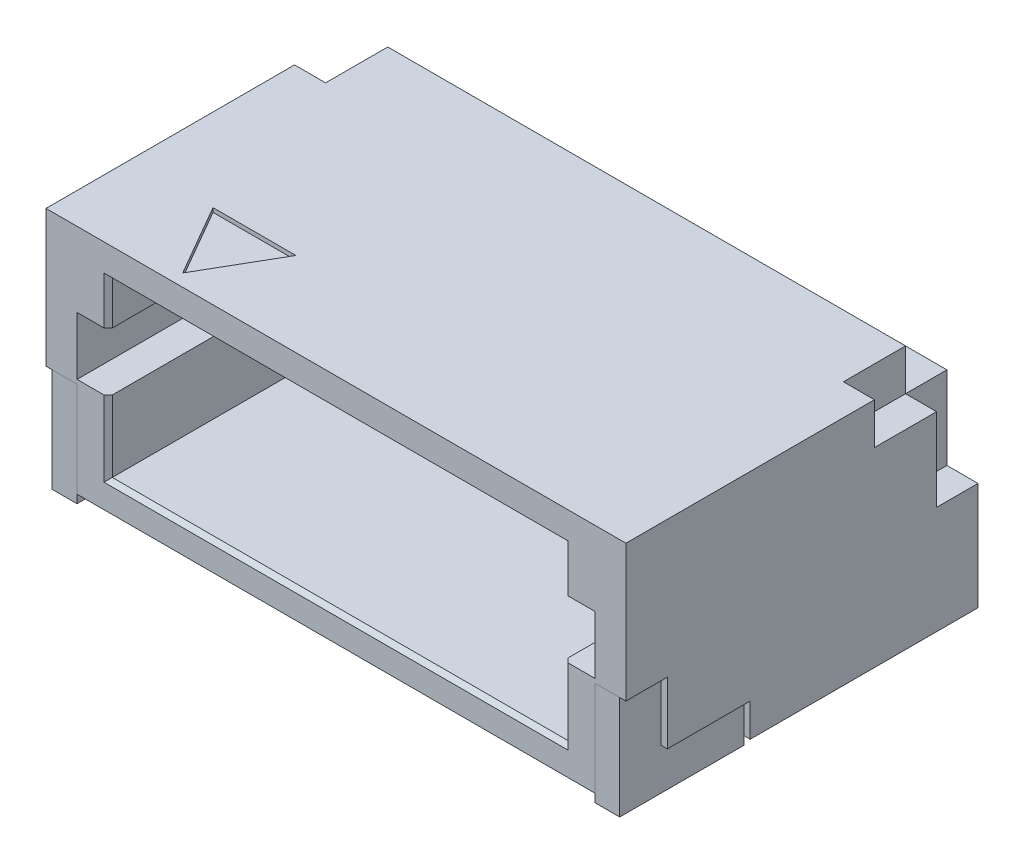
SolidWorks part; units mm, degrees
ref_plane "Front Plane" through (0, 0, 0) normal (0, 0, 1) x (1, 0, 0)
ref_plane "Top Plane" through (0, 0, 0) normal (0, 1, 0) x (1, 0, 0)
ref_plane "Right Plane" through (0, 0, 0) normal (1, 0, 0) x (0, 0, -1)
ref_plane "Right Plane .5mm offset" through (0.5, 0, 0) normal (1, 0, 0) x (0, 0, -1)
sketch "Sketch1" plane through (0, 0, 0) normal (1, 0, 0) x (0, 0, -1)
  line L1 (-4.25, 0) -> (0, 0)
  line L2 (-4.25, 0) -> (-4.25, 2.9)
  line L3 (-4.25, 2.9) -> (0, 2.9)
  line L4 (0, 0) -> (0, 2.9)
  dimension "D1" = 4.25
  dimension "D2" = 2.9
extrude "Extrude1" add sketch "Sketch1" along normal mid plane 7
sketch "Sketch2" plane through (0, 0, 4.25) normal (0, 0, 1) x (1, 0, 0)
  line L0 (2.75, 2) -> (3.125, 2)
  line L1 (-2.75, 0.4375) -> (2.75, 0.4375)
  line L2 (-2.75, 0.4375) -> (-2.75, 1.3)
  line L3 (-2.75, 2.525) -> (2.75, 2.525)
  line L4 (2.75, 0.4375) -> (2.75, 1.3)
  line L5 (3.125, 2) -> (3.125, 1.3)
  line L6 (3.125, 1.3) -> (2.75, 1.3)
  line L7 (-2.75, 2) -> (-3.125, 2)
  line L8 (-3.125, 2) -> (-3.125, 1.3)
  line L9 (-3.125, 1.3) -> (-2.75, 1.3)
  line L10 (2.75, 2) -> (2.75, 2.525)
  line L11 (-2.75, 2) -> (-2.75, 2.525)
  line L12 (-3.5, 2.9) -> (-3.5, 0) construction
  line L13 (3.5, 2.9) -> (3.5, 0) construction
  line L14 (3.5, 2.9) -> (-3.5, 2.9) construction
  line L15 (3.5, 0) -> (-3.5, 0) construction
  dimension "D1" = 2.75
  dimension "D2" = 2.75
  dimension "D3" = 0.375
  dimension "D4" = 0.375
  dimension "D5" = 0.375
  dimension "D6" = 0.4375
  dimension "D7" = 1.6
  dimension "D8" = 0.9
extrude "Extrude2" cut sketch "Sketch2" against normal blind 3.25
sketch "Sketch3" plane through (0, 0, 1) normal (0, 0, 1) x (1, 0, 0)
  line L1 (-0.1, 2.2) -> (0.1, 2.2)
  line L2 (-0.1, 2.2) -> (-0.1, 1.6)
  line L3 (-0.1, 1.6) -> (0.1, 1.6)
  line L4 (0.1, 2.2) -> (0.1, 1.6)
  line L5 (3.5, 2.9) -> (-3.5, 2.9) construction
  point P4 (0, 1.6)
  dimension "D1" = 0.2
  dimension "D2" = 1.3
  dimension "D3" = 0.7
extrude "Extrude3" add sketch "Sketch3" along normal blind 2.25
pattern_linear "LPattern1" count 3 spacing 1 along (-1, 0, 0) count 3 spacing 1 along (1, 0, 0) of "Extrude3"
chamfer "Chamfer1" distance 2 distance2 0.2 10 edges at (0, 1.6, 3.25) (0, 2.2, 3.25) (-2, 2.2, 3.25) (-1, 2.2, 3.25) (2, 2.2, 3.25) (2, 1.6, 3.25) (1, 1.6, 3.25) (-2, 1.6, 3.25) (-1, 1.6, 3.25) (1, 2.2, 3.25) first distance on face at (0, 1.6, 2.125) first distance on face at (0, 2.2, 2.125) first distance on face at (-2, 2.2, 2.125) first distance on face at (-1, 2.2, 2.125) first distance on face at (2, 2.2, 2.125) first distance on face at (2, 1.6, 2.125) first distance on face at (1, 1.6, 2.125) first distance on face at (-2, 1.6, 2.125) first distance on face at (-1, 1.6, 2.125) first distance on face at (1, 2.2, 2.125)
fillet "Fillet1" radius 0.025 40 edges at (2, 1.8, 3.25) (1.9, 1.9, 3.25) (2, 2, 3.25) (2.1, 1.9, 3.25) (1, 1.8, 3.25) (0.9, 1.9, 3.25) (1, 2, 3.25) (1.1, 1.9, 3.25) (0, 2, 3.25) (0.1, 1.9, 3.25) (0, 1.8, 3.25) (-0.1, 1.9, 3.25) (-1, 1.8, 3.25) (-1.1, 1.9, 3.25) (-1, 2, 3.25) (-0.9, 1.9, 3.25) (-2, 1.8, 3.25) (-2.1, 1.9, 3.25) (-2, 2, 3.25) (-1.9, 1.9, 3.25) (-2.1, 2.1, 2.25) (-1.9, 2.1, 2.25) (-2.1, 1.7, 2.25) (-1.9, 1.7, 2.25) (-0.1, 1.7, 2.25) (0.1, 2.1, 2.25) (-0.1, 2.1, 2.25) (0.1, 1.7, 2.25) (2.1, 2.1, 2.25) (1.9, 2.1, 2.25) (2.1, 1.7, 2.25) (1.9, 1.7, 2.25) (0.9, 1.7, 2.25) (1.1, 1.7, 2.25) (1.1, 2.1, 2.25) (0.9, 2.1, 2.25) (-0.9, 2.1, 2.25) (-1.1, 2.1, 2.25) (-1.1, 1.7, 2.25) (-0.9, 1.7, 2.25)
sketch "Sketch4" plane through (3.5, 0, 0) normal (1, 0, 0) x (0, 0, -1)
  line L0 (-4.25, 1.25) -> (-3.75, 1.25)
  line L1 (-4.25, 2.9) -> (-4.25, 0) construction
  line L2 (-3.75, 1.25) -> (-3.75, 0.5)
  line L3 (-3.75, 0.5) -> (-2.75, 0.5)
  line L4 (-2.75, 0.5) -> (-2.75, 0)
  line L5 (-4.25, 0) -> (0, 0) construction
  line L6 (-4.25, 1.25) -> (-4.25, 0)
  line L7 (-4.25, 0) -> (-2.75, 0)
  line L8 (-1.25, 2.9) -> (-1.25, 2.4)
  line L9 (0, 2.9) -> (-4.25, 2.9) construction
  line L10 (-1.25, 2.4) -> (-0.5, 2.4)
  line L11 (-0.5, 2.4) -> (-0.5, 1.4)
  line L12 (-0.5, 1.4) -> (0, 1.4)
  line L13 (0, 0) -> (0, 2.9) construction
  line L14 (0, 1.4) -> (0, 2.9)
  line L15 (-1.25, 2.9) -> (0, 2.9)
  dimension "D1" = 0.5
  dimension "D2" = 0.5
  dimension "D3" = 1.5
  dimension "D4" = 1.25
  dimension "D5" = 0.5
  dimension "D6" = 1.5
  dimension "D7" = 1.25
  dimension "D8" = 0.5
extrude "Extrude4" cut sketch "Sketch4" against normal blind 0.375
mirror "Mirror1" about plane through (0, 0, 0) normal (1, 0, 0) of "Extrude4"
sketch "Sketch8" plane through (3.125, 0, 0) normal (1, 0, 0) x (0, 0, -1)
  line L4 (-2.75, 0.5) -> (-3.75, 0.5)
  line L5 (-2.75, 0.5) -> (-3.75, 0.5)
  line L6 (-4.25, 1.25) -> (-4.25, 0)
  line L7 (-4.25, 0) -> (-2.75, 0)
  line L8 (-2.75, 0) -> (-2.75, 0.5)
  line L11 (-3.75, 0.5) -> (-3.75, 1.25)
  line L12 (-4.25, 1.25) -> (-4.25, 0)
  line L13 (-4.25, 0) -> (-2.75, 0)
  line L14 (-2.75, 0) -> (-2.75, 0.5)
  line L15 (-3.75, 0.5) -> (-3.75, 1.25)
  line L16 (-3.75, 1.25) -> (-4.25, 1.25)
  line L17 (-3.75, 1.25) -> (-4.25, 1.25)
  dimension "D1" = 0
extrude "Extrude7" add sketch "Sketch8" along normal blind 0.3 separate body
sketch "Sketch9" plane through (-3.125, 0, 0) normal (-1, 0, 0) x (0, 0, 1)
  line L4 (4.25, 1.25) -> (3.75, 1.25)
  line L5 (4.25, 1.25) -> (3.75, 1.25)
  line L6 (4.25, 0) -> (4.25, 1.25)
  line L9 (3.75, 1.25) -> (3.75, 0.5)
  line L10 (2.75, 0.5) -> (2.75, 0)
  line L11 (2.75, 0) -> (4.25, 0)
  line L12 (4.25, 0) -> (4.25, 1.25)
  line L13 (3.75, 1.25) -> (3.75, 0.5)
  line L14 (3.75, 0.5) -> (2.75, 0.5)
  line L15 (3.75, 0.5) -> (2.75, 0.5)
  line L16 (2.75, 0.5) -> (2.75, 0)
  line L17 (2.75, 0) -> (4.25, 0)
  dimension "D1" = 0
extrude "Extrude8" add sketch "Sketch9" along normal blind 0.3 separate body
sketch "Sketch6" plane through (0, 0, 0) normal (1, 0, 0) x (0, 0, -1)
  line L0 (-0.5, 2.9) -> (-0.5, 2.4)
  line L1 (0, 2.9) -> (-1.25, 2.9) construction
  line L2 (-0.5, 2.4) -> (0, 2.4)
  line L3 (0, 1.4) -> (0, 2.9) construction
  line L4 (0, 2.4) -> (0, 2.9)
  line L5 (0, 2.9) -> (-0.5, 2.9)
extrude "Extrude5" cut sketch "Sketch6" against normal blind 40.375 and the other way blind 40.375
sketch "Sketch7" plane through (0, 0, 0) normal (0, 1, 0) x (1, 0, 0)
  line L0 (-0.1, 0) -> (-0.1, -0.35)
  line L1 (3.125, 0) -> (-3.125, 0) construction
  line L2 (-0.1, -0.35) -> (0.1, -0.35)
  line L3 (0.1, -0.35) -> (0.1, 0)
  line L4 (0.1, 0) -> (-0.1, 0)
  point P4 (0, -0.35)
  dimension "D1" = 0.2
  dimension "D2" = 0.35
extrude "Extrude6" cut sketch "Sketch7" along normal blind 40.375
pattern_linear "LPattern2" count 3 spacing 1 along (1, 0, 0) count 3 spacing 1 along (-1, 0, 0) of "Extrude6"
chamfer "Chamfer2" distance 0.15 angle 45 10 edges at (0.1, 1.2, 0) (-0.1, 1.2, 0) (2.1, 1.2, 0) (1.9, 1.2, 0) (1.1, 1.2, 0) (0.9, 1.2, 0) (-2.1, 1.2, 0) (-1.9, 1.2, 0) (-0.9, 1.2, 0) (-1.1, 1.2, 0)
sketch "Sketch11" plane through (0, 0, 0) normal (0, -1, 0) x (1, 0, 0)
  line L46 (-3.5, 0) -> (-2.25, 0)
  line L47 (-2.25, 0) -> (-2.1, 0.15)
  line L48 (-2.1, 0.15) -> (-2.1, 0.35)
  line L49 (-2.1, 0.35) -> (-1.9, 0.35)
  line L50 (-1.9, 0.35) -> (-1.9, 0.15)
  line L51 (-1.9, 0.15) -> (-1.75, 0)
  line L52 (-1.75, 0) -> (-1.25, 0)
  line L53 (-1.25, 0) -> (-1.1, 0.15)
  line L54 (-1.1, 0.15) -> (-1.1, 0.35)
  line L55 (-1.1, 0.35) -> (-0.9, 0.35)
  line L56 (-0.9, 0.35) -> (-0.9, 0.15)
  line L57 (-0.9, 0.15) -> (-0.75, 0)
  line L58 (-0.75, 0) -> (-0.25, 0)
  line L59 (-0.25, 0) -> (-0.1, 0.15)
  line L60 (-0.1, 0.15) -> (-0.1, 0.35)
  line L61 (-0.1, 0.35) -> (0.1, 0.35)
  line L62 (0.1, 0.35) -> (0.1, 0.15)
  line L63 (0.1, 0.15) -> (0.25, 0)
  line L64 (0.25, 0) -> (0.75, 0)
  line L65 (0.75, 0) -> (0.9, 0.15)
  line L66 (0.9, 0.15) -> (0.9, 0.35)
  line L67 (0.9, 0.35) -> (1.1, 0.35)
  line L68 (1.1, 0.35) -> (1.1, 0.15)
  line L69 (1.1, 0.15) -> (1.25, 0)
  line L70 (1.25, 0) -> (1.75, 0)
  line L71 (1.75, 0) -> (1.9, 0.15)
  line L72 (1.9, 0.15) -> (1.9, 0.35)
  line L73 (1.9, 0.35) -> (2.1, 0.35)
  line L74 (2.1, 0.35) -> (2.1, 0.15)
  line L75 (2.1, 0.15) -> (2.25, 0)
  line L76 (2.25, 0) -> (3.5, 0)
  line L77 (3.5, 0) -> (3.5, 2.75)
  line L78 (3.5, 2.75) -> (3.125, 2.75)
  line L79 (3.125, 2.75) -> (3.125, 4.25)
  line L80 (3.125, 4.25) -> (-3.125, 4.25)
  line L81 (-3.125, 4.25) -> (-3.125, 2.75)
  line L82 (-3.125, 2.75) -> (-3.5, 2.75)
  line L83 (-3.5, 2.75) -> (-3.5, 0)
  line L90 (-3.5, 0) -> (-2.25, 0)
  line L91 (-2.25, 0) -> (-2.1, 0.15)
  line L92 (-2.1, 0.15) -> (-2.1, 0.35)
  line L93 (-2.1, 0.35) -> (-1.9, 0.35)
  line L94 (-1.9, 0.35) -> (-1.9, 0.15)
  line L95 (-1.9, 0.15) -> (-1.75, 0)
  line L96 (-1.75, 0) -> (-1.25, 0)
  line L97 (-1.25, 0) -> (-1.1, 0.15)
  line L98 (-1.1, 0.15) -> (-1.1, 0.35)
  line L99 (-1.1, 0.35) -> (-0.9, 0.35)
  line L100 (-0.9, 0.35) -> (-0.9, 0.15)
  line L101 (-0.9, 0.15) -> (-0.75, 0)
  line L102 (-0.75, 0) -> (-0.25, 0)
  line L103 (-0.25, 0) -> (-0.1, 0.15)
  line L104 (-0.1, 0.15) -> (-0.1, 0.35)
  line L105 (-0.1, 0.35) -> (0.1, 0.35)
  line L106 (0.1, 0.35) -> (0.1, 0.15)
  line L107 (0.1, 0.15) -> (0.25, 0)
  line L108 (0.25, 0) -> (0.75, 0)
  line L109 (0.75, 0) -> (0.9, 0.15)
  line L110 (0.9, 0.15) -> (0.9, 0.35)
  line L111 (0.9, 0.35) -> (1.1, 0.35)
  line L112 (1.1, 0.35) -> (1.1, 0.15)
  line L113 (1.1, 0.15) -> (1.25, 0)
  line L114 (1.25, 0) -> (1.75, 0)
  line L115 (1.75, 0) -> (1.9, 0.15)
  line L116 (1.9, 0.15) -> (1.9, 0.35)
  line L117 (1.9, 0.35) -> (2.1, 0.35)
  line L118 (2.1, 0.35) -> (2.1, 0.15)
  line L119 (2.1, 0.15) -> (2.25, 0)
  line L120 (2.25, 0) -> (3.5, 0)
  line L121 (3.5, 0) -> (3.5, 2.75)
  line L122 (3.5, 2.75) -> (3.125, 2.75)
  line L123 (3.125, 2.75) -> (3.125, 4.25)
  line L124 (3.125, 4.25) -> (-3.125, 4.25)
  line L125 (-3.125, 4.25) -> (-3.125, 2.75)
  line L126 (-3.125, 2.75) -> (-3.5, 2.75)
  line L127 (-3.5, 2.75) -> (-3.5, 0)
  dimension "D1" = 0
extrude "Extrude10" cut sketch "Sketch11" against normal blind 0.1
sketch "Sketch10" plane through (0, 0, 0) normal (1, 0, 0) x (0, 0, -1)
  line L0 (-0.35, 2.4) -> (-0.35, 0.25)
  line L1 (-0.1, 0) -> (0.625, 0)
  line L2 (0.7, 0.075) -> (0.7, 0.125)
  line L3 (0.625, 0.2) -> (0.2, 0.2)
  line L4 (0.2, 0.2) -> (0, 0.5464)
  line L5 (0, 0.1) -> (0, 1.4) construction
  line L6 (0, 1.4) -> (0, 2.4) construction
  line L7 (0, 0.5464) -> (0, 2.4)
  line L8 (0, 2.4) -> (-0.5, 2.4) construction
  line L9 (0, 2.4) -> (-0.35, 2.4)
  line L10 (-0.35, 0.25) -> (-0.1, 0)
  arc A0 (0.7, 0.125) -> (0.625, 0.2) centre (0.625, 0.125) ccw
  arc A1 (0.625, 0) -> (0.7, 0.075) centre (0.625, 0.075) ccw
  point P1 (-0.35, 0)
  point P14 (0.7, 0.2)
  point P17 (0.7, 0)
  dimension "D6" = 0.075
  dimension "D1" = 0.35
  dimension "D2" = 0.7
  dimension "D3" = 0.5
  dimension "D4" = 120
  dimension "D5" = 0.2
extrude "Extrude9" add sketch "Sketch10" along normal mid plane 0.2 separate body
pattern_linear "LPattern3" count 3 spacing 1 along (-1, 0, 0) count 3 spacing 1 along (1, 0, 0) of bodies 114
sketch "Sketch12" plane through (0, 0, 1) normal (0, 0, 1) x (1, 0, 0)
  line L1 (-0.1, 1.1625) -> (0.1, 1.1625)
  line L2 (-0.1, 1.1625) -> (-0.1, 0.7625)
  line L3 (-0.1, 0.7625) -> (0.1, 0.7625)
  line L4 (0.1, 1.1625) -> (0.1, 0.7625)
  line L5 (3.5, 2.9) -> (-3.5, 2.9) construction
  point P6 (0, 0.7625)
  dimension "D1" = 0.2
  dimension "D2" = 0.4
  dimension "D3" = 1.7375
extrude "Extrude11" cut sketch "Sketch12" against normal blind 0.05
pattern_linear "LPattern4" count 3 spacing 1 along (1, 0, 0) count 3 spacing 1 along (-1, 0, 0) of "Extrude11"
chamfer "Chamfer3" distance 0.05 angle 45 6 edges at (2.75, 2.2625, 4.25) (2.75, 0.8687, 4.25) (0, 0.4375, 4.25) (-2.75, 0.8687, 4.25) (-2.75, 2.2625, 4.25) (0, 2.525, 4.25)
sketch "Sketch13" plane through (0, 2.9, 0) normal (0, 1, 0) x (1, 0, 0)
  line L0 (-2, -4.1) -> (-2.5, -3.234)
  line L1 (-2.5, -3.234) -> (-1.5, -3.234)
  line L2 (-1.5, -3.234) -> (-2, -4.1)
  line L4 (3.5, -4.25) -> (-3.5, -4.25) construction
  line L5 (-1.9, 0.625) -> (-2.1, 0.625) construction
  point P10 (-2, 0.625)
  dimension "D1" = 1
  dimension "D2" = 0.15
extrude "Pin 1 mark" cut sketch "Sketch13" against normal blind 0.05
sketch "Sketch - SMT pads with centroid of pin 1" plane through (0, 0, 0) normal (0, -1, 0) x (1, 0, 0)
  line L0 (-2.3, 0.25) -> (-1.7, -1.3) construction
  line L1 (-2.3, -1.3) -> (-1.7, -1.3) construction
  line L2 (-2.3, -1.3) -> (-2.3, 0.25) construction
  line L3 (-2.3, 0.25) -> (-1.7, 0.25) construction
  line L4 (-1.7, -1.3) -> (-1.7, 0.25) construction
  line L5 (-3.9, 4.45) -> (-2.7, 4.45) construction
  line L6 (-3.9, 4.45) -> (-3.9, 2.65) construction
  line L7 (-3.9, 2.65) -> (-2.7, 2.65) construction
  line L8 (-2.7, 4.45) -> (-2.7, 2.65) construction
  line L9 (2.7, 4.45) -> (3.9, 4.45) construction
  line L10 (2.7, 4.45) -> (2.7, 2.65) construction
  line L11 (2.7, 2.65) -> (3.9, 2.65) construction
  line L12 (3.9, 4.45) -> (3.9, 2.65) construction
  line L15 (1.9, 0.35) -> (2.1, 0.35) construction
  line L16 (-2, -0.525) -> (2.3, -0.525) construction
  line L32 (-1.3, -1.3) -> (-1.3, 0.25) construction
  line L33 (-1.3, -1.3) -> (-0.7, -1.3) construction
  line L34 (3.125, 4.25) -> (-3.125, 4.25) construction
  line L35 (-0.7, -1.3) -> (-0.7, 0.25) construction
  line L36 (-1.3, 0.25) -> (-0.7, 0.25) construction
  line L37 (-0.3, -1.3) -> (-0.3, 0.25) construction
  line L38 (-0.3, -1.3) -> (0.3, -1.3) construction
  line L39 (0.3, -1.3) -> (0.3, 0.25) construction
  line L40 (-0.3, 0.25) -> (0.3, 0.25) construction
  line L41 (0.7, -1.3) -> (0.7, 0.25) construction
  line L42 (0.7, -1.3) -> (1.3, -1.3) construction
  line L43 (1.3, -1.3) -> (1.3, 0.25) construction
  line L44 (0.7, 0.25) -> (1.3, 0.25) construction
  line L45 (1.7, -1.3) -> (1.7, 0.25) construction
  line L46 (1.7, -1.3) -> (2.3, -1.3) construction
  line L47 (2.3, -1.3) -> (2.3, 0.25) construction
  line L48 (1.7, 0.25) -> (2.3, 0.25) construction
  point P4 (-2, -0.525)
  point P13 (2, 0.35)
  dimension "D1" = 0.6
  dimension "D2" = 1.2
  dimension "D3" = 1.8
  dimension "D4" = 0.7
  dimension "D5" = 5.55
  dimension "D6" = 4
  dimension "D7" = 0.2
  dimension "D8" = 2
  dimension "D9" = 0.7
  dimension "D10" = 1
  dimension "D11" = 5
